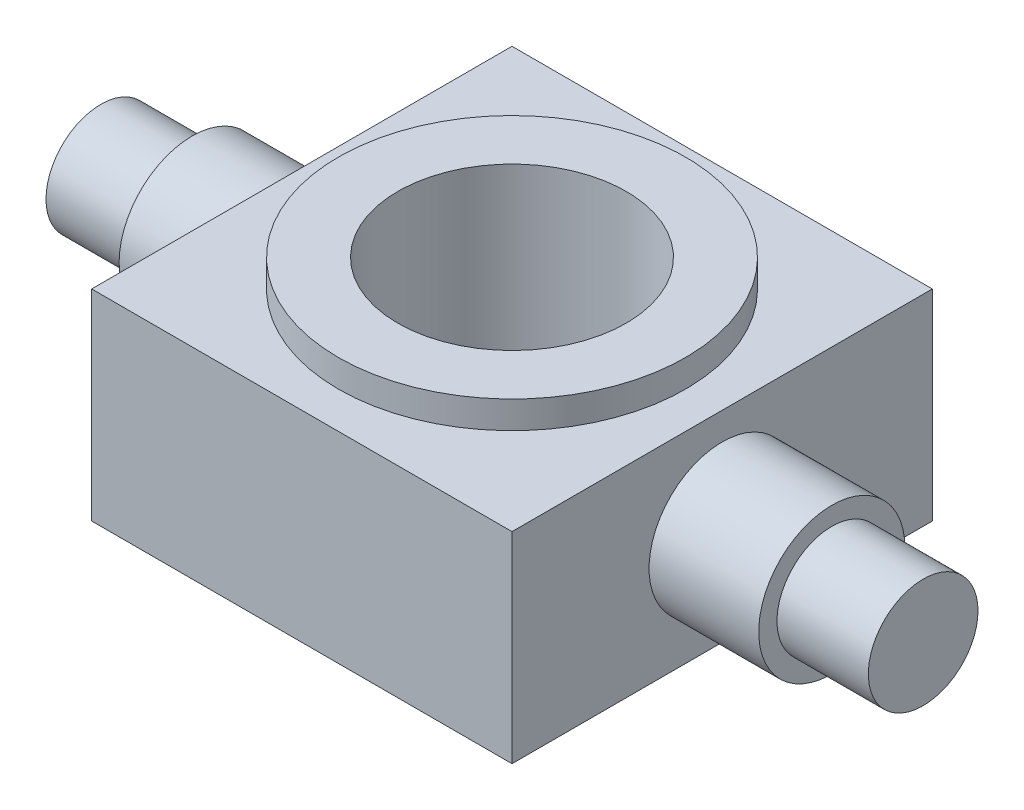
SolidWorks part; units mm, degrees
ref_plane "Plano frontal" through (0, 0, 0) normal (0, 0, 1) x (1, 0, 0)
ref_plane "Plano superior" through (0, 0, 0) normal (0, 1, 0) x (1, 0, 0)
ref_plane "Plano direito" through (0, 0, 0) normal (1, 0, 0) x (0, 0, -1)
sketch "Esboço1" plane through (0, 0, 0) normal (0, 1, 0) x (1, 0, 0)
  line L0 (-85.9509, 0) -> (89.5122, 0) construction
  line L1 (-23, 23) -> (23, 23)
  line L2 (-23, 23) -> (-23, -23)
  line L3 (-23, -23) -> (23, -23)
  line L4 (23, 23) -> (23, -23)
  line L5 (-23, 23) -> (23, -23) construction
  line L6 (-23, -23) -> (23, 23) construction
  line L7 (0, 59.0764) -> (0, -70.3848) construction
  circle A0 centre (0, 0) radius 12.5
  circle A1 centre (0, 0) radius 16
  circle A2 centre (0, 0) radius 19
  dimension "D1" = 25
  dimension "D2" = 32
  dimension "D3" = 38
  dimension "D4" = 46
  dimension "D5" = 46
extrude "Ressalto-extrusão1" add sketch "Esboço1" along normal blind 22 contours L4 L1 L2 L3 A2 | A2 A1 | A1 A0 region at (0, 0, -22.3495) region at (-15.5475, 0, 0) region at (-18.4626, 0, 0)
extrude "Ressalto-extrusão4" add sketch "Esboço1<7>" along normal blind 25 contours A2 A1 | A1 A0 region at (-15.5475, 0, 0) region at (-18.4626, 0, 0)
sketch "Esboço1<7>" plane through (0, 0, 0) normal (0, 1, 0) x (1, 0, 0) same geometry as "Esboço1"
extrude "Ressalto-extrusão5" add sketch "Esboço1<8>" against normal blind 3 contours A2 A1 | A1 A0 region at (-15.5475, 0, 0) region at (-18.4626, 0, 0)
sketch "Esboço1<8>" plane through (0, 0, 0) normal (0, 1, 0) x (1, 0, 0) same geometry as "Esboço1"
sketch "Esboço7" plane through (-23, 0, 0) normal (-1, 0, 0) x (0, 0, 1)
  line L0 (0, 42.5853) -> (0, -25.7968) construction
  line L2 (-23, 0) -> (23, 0) construction
  circle A0 centre (0, 11) radius 8
  circle A1 centre (0, 11) radius 6
  dimension "D1" = 16
  dimension "D2" = 11
  dimension "D3" = 12
extrude "Ressalto-extrusão8" add sketch "Esboço7" along normal blind 12
extrude "Ressalto-extrusão9" add sketch "Esboço7<3>" along normal blind 22 contours L0 A1 | A1 L0 region at (-23, 11, 2.5465) region at (-23, 11, -2.5465)
sketch "Esboço7<3>" plane through (-23, 0, 0) normal (-1, 0, 0) x (0, 0, 1) same geometry as "Esboço7"
sketch "Esboço8" plane through (23, 0, 0) normal (1, 0, 0) x (0, 0, -1)
  line L0 (0, 44.2934) -> (0, -37.3937) construction
  line L1 (23, 0) -> (-23, 0) construction
  circle A0 centre (0, 11) radius 6
  circle A1 centre (0, 11) radius 8
  dimension "D1" = 12
  dimension "D2" = 16
  dimension "D3" = 11
extrude "Ressalto-extrusão10" add sketch "Esboço8" along normal blind 12
extrude "Ressalto-extrusão11" add sketch "Esboço8<2>" along normal blind 22 contours L0 A0 | A0 L0 region at (23, 11, -2.5465) region at (23, 11, 2.5465)
sketch "Esboço8<2>" plane through (23, 0, 0) normal (1, 0, 0) x (0, 0, -1) same geometry as "Esboço8"
